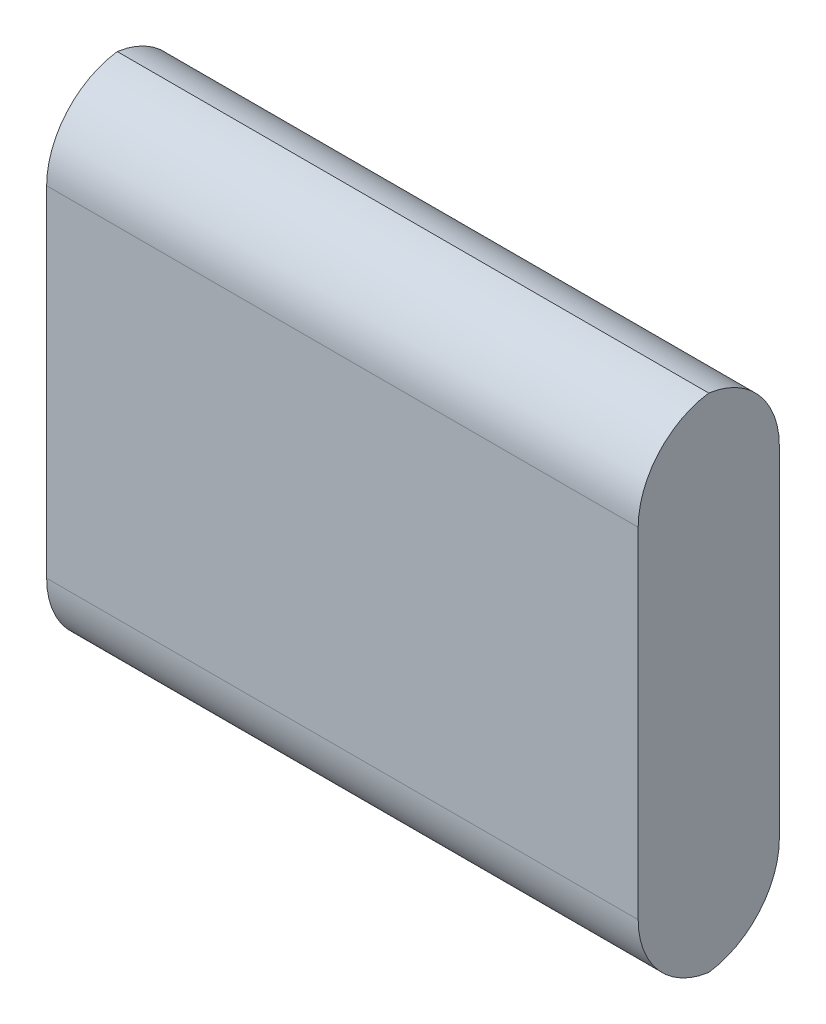
SolidWorks part; units mm, degrees
ref_plane "前基準面" through (0, 0, 0) normal (0, 0, 1) x (1, 0, 0)
ref_plane "上基準面" through (0, 0, 0) normal (0, 1, 0) x (1, 0, 0)
ref_plane "右基準面" through (0, 0, 0) normal (1, 0, 0) x (0, 0, -1)
sketch "草圖1" plane through (0, 0, 0) normal (0, 0, 1) x (1, 0, 0)
  line L1 (45.25, 38.5) -> (-45.25, 38.5)
  line L2 (45.25, 38.5) -> (45.25, -38.5)
  line L3 (45.25, -38.5) -> (-45.25, -38.5)
  line L4 (-45.25, 38.5) -> (-45.25, -38.5)
  line L5 (45.25, 38.5) -> (-45.25, -38.5) construction
  line L6 (45.25, -38.5) -> (-45.25, 38.5) construction
  point P0 (0, 0)
  dimension "D1" = 90.5
  dimension "D2" = 77
extrude "填料-伸長1" add sketch "草圖1" along normal blind 21.6
fillet "圓角1" radius 12.5 4 edges at (0, -38.5, 0) (0, -38.5, 21.6) (0, 38.5, 0) (0, 38.5, 21.6)
